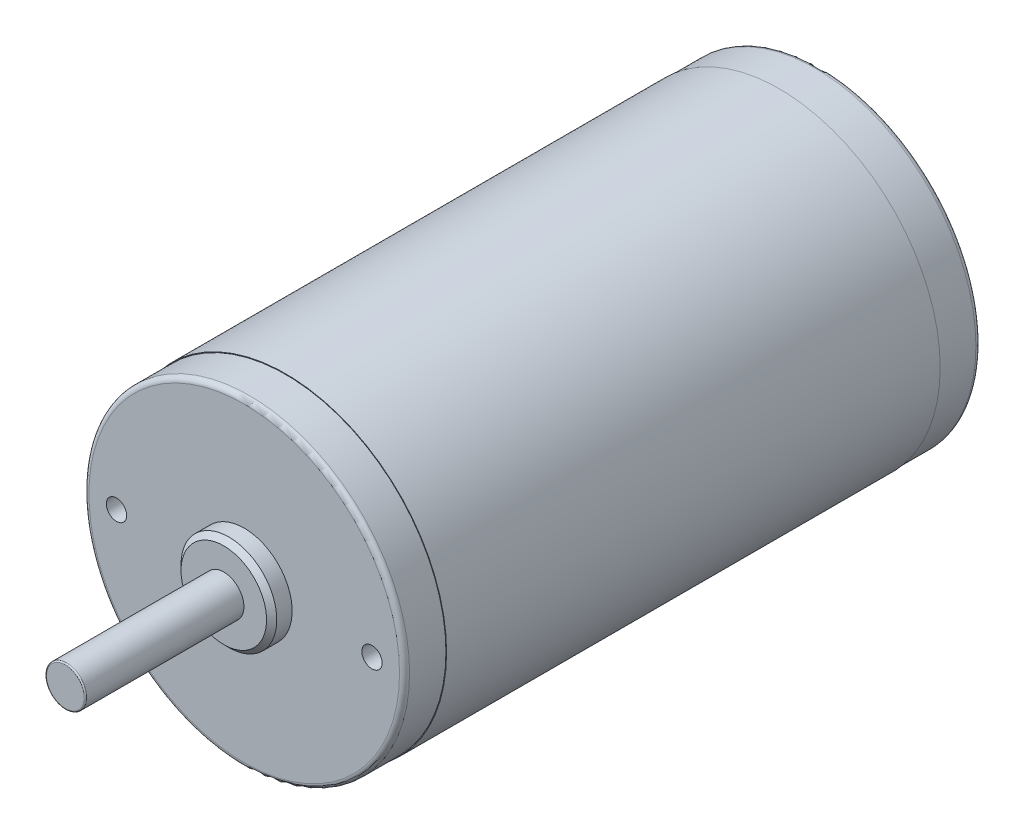
SolidWorks part; units mm, degrees
ref_plane "Front Plane" through (0, 0, 0) normal (0, 0, 1) x (1, 0, 0)
ref_plane "Top Plane" through (0, 0, 0) normal (0, 1, 0) x (1, 0, 0)
ref_plane "Right Plane" through (0, 0, 0) normal (1, 0, 0) x (0, 0, -1)
ref_plane "Plane1" through (0, 109.2962, 0) normal (0, -1, 0) x (1, 0, 0)
sketch "Sketch1" plane through (0, 109.2962, 0) normal (0, -1, 0) x (1, 0, 0)
  line L0 (67.564, 10.8204) -> (35.56, 10.8204)
  line L1 (35.56, 10.8204) -> (35.56, -87.3252)
  line L2 (35.56, -87.3252) -> (67.564, -87.3252)
  line L3 (67.564, -87.3252) -> (67.564, 10.8204)
  line L4 (35.56, 10.8204) -> (35.56, -87.3252) construction
revolve "Revolve1" add sketch "Sketch1" angle 360 about L4 reverse direction yes
sketch "Sketch2" plane through (0, 0, 10.8204) normal (0, 0, 1) x (1, 0, 0)
  circle A0 centre (35.56, 109.2962) radius 31.877
extrude "Boss-Extrude1" add sketch "Sketch2" along normal blind 8.2296
ref_plane "Plane2" through (0, 0, 18.542) normal (0, 0, -1) x (-1, 0, 0)
sketch "Sketch5" plane through (0, 0, 18.542) normal (0, 0, -1) x (-1, 0, 0)
  circle A0 centre (-35.56, 109.2962) radius 9.525
extrude "Boss-Extrude2" add sketch "Sketch5" against normal blind 4.572
sketch "Sketch6" plane through (0, 0, 23.114) normal (0, 0, 1) x (1, 0, 0)
  circle A0 centre (35.56, 109.2962) radius 4
extrude "Boss-Extrude3" add sketch "Sketch6" along normal blind 31.5
sketch "Sketch8" plane through (0, 0, -87.3252) normal (0, 0, -1) x (-1, 0, 0)
  circle A0 centre (-35.56, 109.2962) radius 31.877
extrude "Boss-Extrude4" add sketch "Sketch8" along normal blind 8.2296
sketch "Sketch9" plane through (0, 0, -95.5548) normal (0, 0, -1) x (-1, 0, 0)
  circle A0 centre (-35.56, 109.2962) radius 15.0368
extrude "Boss-Extrude5" add sketch "Sketch9" along normal blind 4.7625
ref_plane "Plane3" [suppressed] through (0, 120.5036, 0) normal (0, 1, 0) x (-1, 0, 0)
sketch "Sketch10" [suppressed] plane through (0, 120.5036, 0) normal (0, 1, 0) x (-1, 0, 0)
  line L0 (-56.2851, -97.8027) -> (-54.1671, -97.8027)
  line L1 (-54.1671, -97.8027) -> (-54.1671, -95.5548)
  line L2 (-54.1671, -95.5548) -> (-58.4851, -95.5548)
  line L3 (-58.4851, -95.5548) -> (-58.4851, -95.6027)
  line L4 (-58.4851, -95.6027) -> (-56.2851, -97.8027)
  line L5 (-54.1671, -97.8027) -> (-54.1671, -95.5548) construction
revolve "Revolve2" [suppressed] add sketch "Sketch10" angle 360 about L5 reverse direction yes
ref_plane "Plane4" [suppressed] through (0, 127.9033, 0) normal (0, 1, 0) x (-1, 0, 0)
sketch "Sketch11" [suppressed] plane through (0, 127.9033, 0) normal (0, 1, 0) x (-1, 0, 0)
  line L0 (-48.8854, -97.8027) -> (-46.7674, -97.8027)
  line L1 (-46.7674, -97.8027) -> (-46.7674, -95.5548)
  line L2 (-46.7674, -95.5548) -> (-51.0854, -95.5548)
  line L3 (-51.0854, -95.5548) -> (-51.0854, -95.6027)
  line L4 (-51.0854, -95.6027) -> (-48.8854, -97.8027)
  line L5 (-46.7674, -97.8027) -> (-46.7674, -95.5548) construction
revolve "Revolve3" [suppressed] add sketch "Sketch11" angle 360 about L5 reverse direction yes
hole_wizard "Hole2" positions "Sketch13" profile "Sketch12" legacy
sketch "Sketch13" plane through (0, 0, 19.05) normal (0, 0, 1) x (1, 0, 0)
  point P0 (60.96, 109.2962)
sketch "Sketch12" plane through (60.96, 109.2962, 19.05) normal (1, 0, 0) x (0, -1, 0)
  line L0 (0, 0) -> (0, 14.8277)
  line L1 (0, 14.8277) -> (2.0193, 13.6144)
  line L2 (2.0193, 13.6144) -> (2.0193, 0)
  line L4 (2.0193, 0) -> (0, 0)
  line L6 (0, 14.8277) -> (-2.0193, 13.6144) construction
  line L7 (0, -4.2442) -> (0, 117.3081) construction
  dimension "Diameter" = 4.0386
  dimension "Depth" = 13.6144
  dimension "Drill Angle" = 118
hole_wizard "Hole3" positions "Sketch15" profile "Sketch14" legacy
sketch "Sketch15" plane through (0, 0, 19.05) normal (0, 0, 1) x (1, 0, 0)
  point P0 (10.16, 109.2962)
sketch "Sketch14" plane through (10.16, 109.2962, 19.05) normal (1, 0, 0) x (0, -1, 0)
  line L0 (0, 0) -> (0, 14.8277)
  line L1 (0, 14.8277) -> (2.0193, 13.6144)
  line L2 (2.0193, 13.6144) -> (2.0193, 0)
  line L4 (2.0193, 0) -> (0, 0)
  line L6 (0, 14.8277) -> (-2.0193, 13.6144) construction
  line L7 (0, -4.2442) -> (0, 117.3081) construction
  dimension "Diameter" = 4.0386
  dimension "Depth" = 13.6144
  dimension "Drill Angle" = 118
chamfer "Chamfer1" distance 1.016 angle 45 1 edges at (45.085, 109.2962, 23.114) first distance on face at (45.085, 109.2962, 23.114)
fillet "Fillet1" radius 0.254 1 edges at (39.56, 109.2962, 54.614) tangent propagation no
fillet "Fillet2" radius 1 1 edges at (3.683, 109.2962, -95.5548) tangent propagation no
fillet "Fillet3" radius 1 1 edges at (67.437, 109.2962, 19.05) tangent propagation no
fillet "Fillet4" radius 1 1 edges at (20.5232, 109.2962, -100.3173) tangent propagation no
ref_plane "Plane5" [suppressed] through (39.56, 0, 0) normal (1, 0, 0) x (0, 0, -1)
sketch "Sketch16" [suppressed] plane through (39.56, 0, 0) normal (1, 0, 0) x (0, 0, -1)
  line L0 (-26.05, 109.2962) -> (-23.114, 109.2962)
  line L1 (-26.05, 110.3462) -> (-46.15, 110.3462)
  line L2 (-26.05, 110.3462) -> (-26.05, 108.2462)
  line L3 (-26.05, 108.2462) -> (-46.15, 108.2462)
  line L4 (-46.15, 110.3462) -> (-46.15, 108.2462)
  line L5 (-23.114, 113.2962) -> (-23.114, 105.2962) construction
  line L6 (-19.05, 140.1732) -> (-19.05, 78.4192) construction
  dimension "D1" = 7
  dimension "D2" = 2.1
  dimension "D3" = 20.1
extrude "Cut-Extrude2" [suppressed] cut sketch "Sketch16" against normal blind 1.2 contours L1 L4 L3 L2
fillet "Fillet5" [suppressed] radius 1.05
